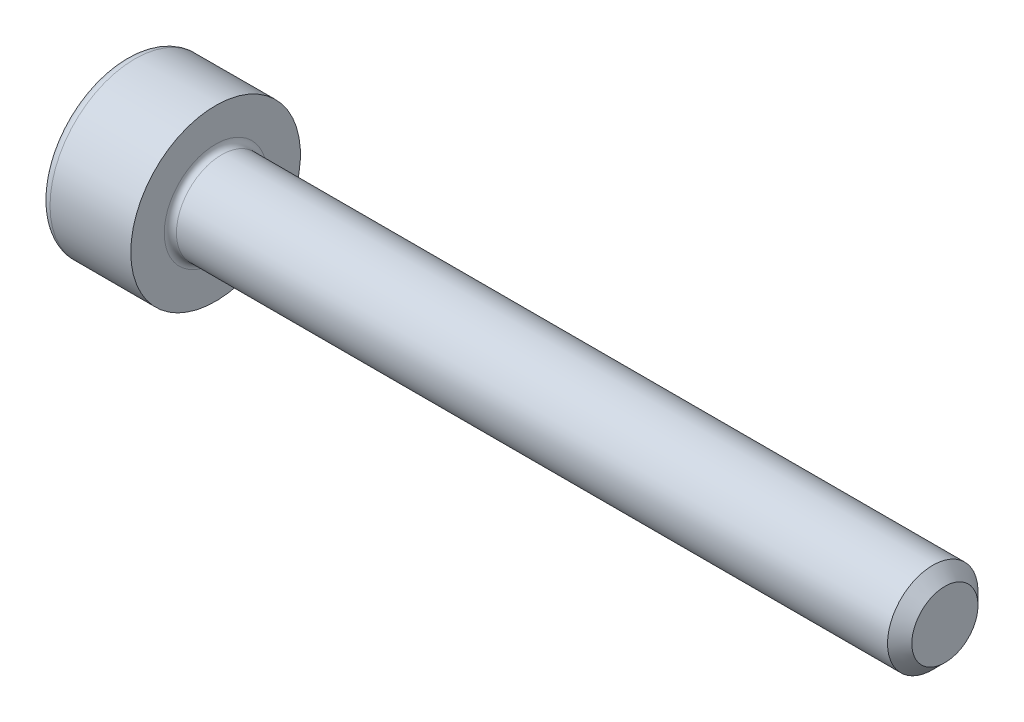
SolidWorks part; units mm, degrees
ref_plane "Спереди" through (0, 0, 0) normal (0, 0, 1) x (1, 0, 0)
ref_plane "Сверху" through (0, 0, 0) normal (0, 1, 0) x (1, 0, 0)
ref_plane "Справа" through (0, 0, 0) normal (1, 0, 0) x (0, 0, -1)
sketch "Sketch1" plane through (0, 0, 0) normal (0, 0, 1) x (1, 0, 0)
  line L0 (0, 0) -> (1.4887, 0)
  line L1 (1.4887, 0) -> (1.4887, 1.3957)
  line L2 (1.4887, 1.3957) -> (0, 1.3957)
  line L3 (0, 1.3957) -> (0, 0)
  line L4 (1.4887, 0) -> (13.4887, 0)
  line L5 (13.4887, 0) -> (13.4887, 0.7444)
  line L6 (13.4887, 0.7444) -> (1.4887, 0.7444)
  dimension "D1" = 12
revolve "Revolve1" add sketch "Sketch1" angle 360 about L0 region at (0.7444, 0.6978, 0) region at (7.4887, 0.3722, 0)
fillet "Fillet1" radius 0.1 1 edges at (1.4887, 0, 0.7444)
fillet "Fillet2" radius 0.16 1 edges at (0, 0, 1.3957)
chamfer "Chamfer1" distance 0.2 angle 45 1 edges at (13.4887, 0, 0.7444)
sketch "Sketch2" plane through (0, 0, 0) normal (-1, 0, 0) x (0, 0, 1)
  line L1 (0, 0.8776) -> (-0.76, 0.4388)
  line L2 (-0.76, 0.4388) -> (-0.76, -0.4388)
  line L3 (-0.76, -0.4388) -> (0, -0.8776)
  line L4 (0, -0.8776) -> (0.76, -0.4388)
  line L5 (0.76, -0.4388) -> (0.76, 0.4388)
  line L6 (0.76, 0.4388) -> (0, 0.8776)
  circle A0 centre (0, 0) radius 0.76 construction
extrude "Extrude1" cut sketch "Sketch2" against normal blind 0.7
